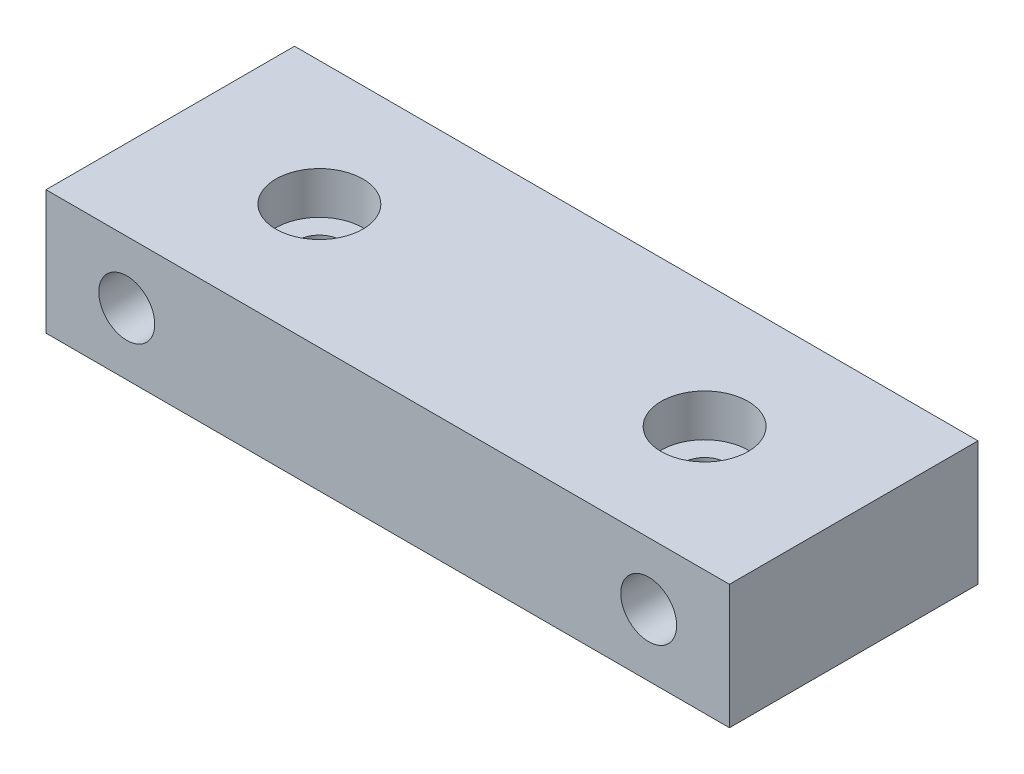
SolidWorks part; units mm, degrees
material "ABS"
ref_plane "Front Plane" through (0, 0, 0) normal (0, 0, 1) x (1, 0, 0)
ref_plane "Top Plane" through (0, 0, 0) normal (0, 1, 0) x (1, 0, 0)
ref_plane "Right Plane" through (0, 0, 0) normal (1, 0, 0) x (0, 0, -1)
sketch "Sketch1" plane through (0, 0, 0) normal (0, 1, 0) x (1, 0, 0)
  line L1 (-27.5, -10) -> (27.5, -10)
  line L2 (-27.5, -10) -> (-27.5, 10)
  line L3 (-27.5, 10) -> (27.5, 10)
  line L4 (27.5, -10) -> (27.5, 10)
  line L5 (-27.5, -10) -> (27.5, 10) construction
  line L6 (-27.5, 10) -> (27.5, -10) construction
  point P0 (0, 0)
  dimension "D1" = 55
  dimension "D2" = 20
extrude "Boss-Extrude1" add sketch "Sketch1" along normal blind 10
sketch "Sketch2" plane through (0, 0, 10) normal (0, 0, 1) x (1, 0, 0)
  line L0 (-27.5, 0) -> (27.5, 0) construction
  line L1 (-27.5, 10) -> (-27.5, 0) construction
  circle A0 centre (-21, 5) radius 2.25
  circle A1 centre (21, 5) radius 2.25
  dimension "D1" = 4.5
  dimension "D4" = 4.5
  dimension "D2" = 5
  dimension "D3" = 6.5
  dimension "D5" = 42
extrude "Cut-Extrude1" cut sketch "Sketch2" against normal through all
sketch "Sketch3" plane through (0, 10, 0) normal (0, 1, 0) x (1, 0, 0)
  line L0 (27.5, -10) -> (27.5, 10) construction
  line L1 (-27.5, 10) -> (-27.5, -10) construction
  circle A0 centre (-15.5, 0) radius 1.75
  circle A1 centre (15.5, 0) radius 1.75
  dimension "D1" = 3.5
  dimension "D2" = 3.5
  dimension "D3" = 12
  dimension "D4" = 12
extrude "Cut-Extrude2" cut sketch "Sketch3" against normal through all
hole_wizard "CBORE for M3 Hex Socket Head Cap Screw1" positions "Sketch4" profile "Sketch5" counterbore size "M3" standard "ISO" end condition through all
sketch "Sketch4" plane through (0, 10, 0) normal (0, 1, 0) x (1, 0, 0)
  point P0 (-15.5, 0)
  point P3 (15.5, 0)
sketch "Sketch5" plane through (-15.5, 10, 0) normal (1, 0, 0) x (0, 0, 1)
  line L0 (0, 0) -> (0, 10)
  line L1 (0, 10) -> (1.7, 10)
  line L3 (1.7, 10) -> (1.7, 3.4)
  line L4 (1.7, 3.4) -> (3.5, 3.4)
  line L5 (3.5, 3.4) -> (3.5, 0)
  line L7 (3.5, 0) -> (0, 0)
  line L11 (0, -6.35) -> (0, 107.95) construction
  dimension "Thru Hole Dia." = 3.4
  dimension "Thru Hole Depth" = 10
  dimension "C'Bore Dia." = 7
  dimension "C'Bore Depth" = 3.4
sketch "Sketch6" plane through (0, 0, -10) normal (0, 0, -1) x (-1, 0, 0)
  line L13 (-16.3812, 5) -> (-18.6906, 9)
  line L14 (-18.6906, 9) -> (-23.3094, 9)
  line L15 (-23.3094, 9) -> (-25.6188, 5)
  line L16 (-25.6188, 5) -> (-23.3094, 1)
  line L17 (-23.3094, 1) -> (-18.6906, 1)
  line L18 (-18.6906, 1) -> (-16.3812, 5)
  line L19 (16.3812, 5) -> (18.6906, 1)
  line L20 (18.6906, 1) -> (23.3094, 1)
  line L21 (23.3094, 1) -> (25.6188, 5)
  line L22 (25.6188, 5) -> (23.3094, 9)
  line L23 (23.3094, 9) -> (18.6906, 9)
  line L24 (18.6906, 9) -> (16.3812, 5)
  circle A0 centre (-21, 5) radius 4 construction
  circle A1 centre (21, 5) radius 4 construction
  dimension "D1" = 8
  dimension "D2" = 8
extrude "Cut-Extrude3" cut sketch "Sketch6" against normal blind 4
